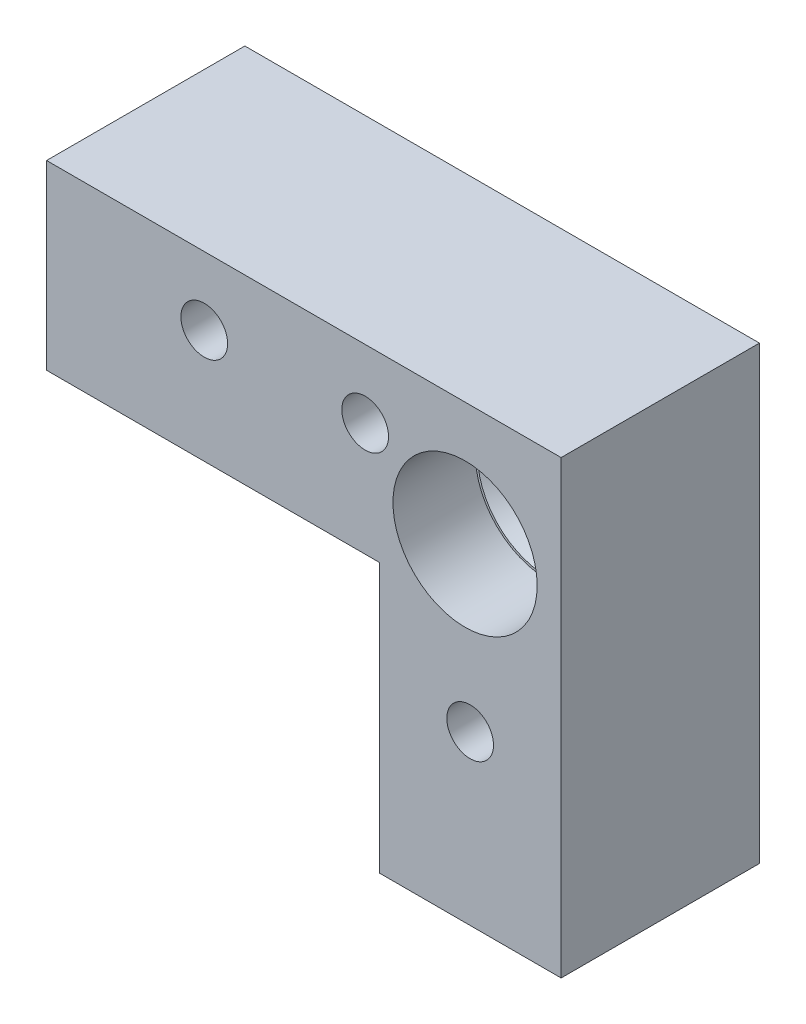
SolidWorks part; units mm, degrees
material "Rubber"
ref_plane "Front Plane" through (0, 0, 0) normal (0, 0, 1) x (1, 0, 0)
ref_plane "Top Plane" through (0, 0, 0) normal (0, 1, 0) x (1, 0, 0)
ref_plane "Right Plane" through (0, 0, 0) normal (1, 0, 0) x (0, 0, -1)
sketch "Sketch1" plane through (0, 0, 0) normal (0, 0, 1) x (1, 0, 0)
  line L1 (0, 0) -> (14, 0)
  line L2 (0, 0) -> (0, -34.73)
  line L3 (0, -34.73) -> (14, -34.73)
  line L4 (14, 0) -> (14, -34.73)
  line L5 (0, 0) -> (-25.65, 0)
  line L6 (0, 0) -> (0, -14)
  line L7 (0, -14) -> (-25.65, -14)
  line L8 (-25.65, 0) -> (-25.65, -14)
  dimension "D1" = 14
  dimension "D2" = 39.65
  dimension "D3" = 34.73
extrude "Boss-Extrude1" add sketch "Sketch1" along normal blind 42.65 contours L5 L8 L7 L2 | L4 L1 L2 L3 region at (7, -17.365, 0) region at (-12.825, -7, 0)
sketch "Sketch2" plane through (0, -14, 0) normal (0, -1, 0) x (1, 0, 0)
  line L0 (-25.65, 42.65) -> (-25.65, 0) construction
  line L1 (0, 42.65) -> (-25.65, 42.65) construction
  circle A0 centre (-14.665, 27.725) radius 6.425
  point P2 (-21.09, 27.725)
  point P6 (-14.665, 34.15)
  dimension "D1" = 12.85
  dimension "D2" = 4.56
  dimension "D3" = 8.5
extrude "Cut-Extrude1" cut sketch "Sketch2" against normal blind 42.65
sketch "Sketch3" plane through (0, -14, 0) normal (0, -1, 0) x (1, 0, 0)
  line L0 (0, 42.65) -> (-25.65, 42.65) construction
  line L1 (-17.65, 42.65) -> (-15.75, 42.65)
  line L2 (-17.65, 42.65) -> (-17.65, 12.65)
  line L3 (-17.65, 12.65) -> (-15.75, 12.65)
  line L4 (-15.75, 42.65) -> (-15.75, 12.65)
  line L5 (-25.65, 42.65) -> (-25.65, 0) construction
  dimension "D1" = 8
  dimension "D2" = 1.9
  dimension "D3" = 30
extrude "Cut-Extrude2" cut sketch "Sketch3" against normal blind 42.65
sketch "Sketch4" plane through (0, 0, 0) normal (-1, 0, 0) x (0, 0, 1)
  line L0 (42.65, -34.73) -> (0, -34.73) construction
  line L1 (42.65, -14) -> (42.65, -34.73) construction
  circle A0 centre (18.725, -21.745) radius 6.425
  point P2 (25.15, -21.745)
  point P3 (18.725, -28.17)
  dimension "D1" = 12.85
  dimension "D2" = 6.56
  dimension "D3" = 17.5
extrude "Cut-Extrude3" cut sketch "Sketch4" against normal blind 42.65
sketch "Sketch5" plane through (0, 0, 0) normal (-1, 0, 0) x (0, 0, 1)
  line L0 (42.65, -14) -> (42.65, -34.73) construction
  line L1 (42.65, -26.73) -> (10.65, -26.73)
  line L2 (42.65, -26.73) -> (42.65, -24.83)
  line L3 (42.65, -24.83) -> (10.65, -24.83)
  line L4 (10.65, -26.73) -> (10.65, -24.83)
  line L5 (42.65, -34.73) -> (0, -34.73) construction
  dimension "D1" = 8
  dimension "D2" = 1.9
  dimension "D3" = 32
extrude "Cut-Extrude4" cut sketch "Sketch5" against normal blind 42.65
hole_wizard "M3 Clearance Hole1" positions "Sketch6" profile "Sketch8" hole size "M3" standard "ANSI Metric"
sketch "Sketch6" plane through (0, 0, 0) normal (0, 0, -1) x (-1, 0, 0)
  line L0 (-14, 0) -> (25.65, 0) construction
  line L1 (25.65, 0) -> (25.65, -14) construction
  line L2 (-14, 0) -> (-14, -34.73) construction
  point P0 (1.1, -5.25)
  point P2 (13.5, -5.25)
  point P4 (-6.99, -21.8)
  dimension "D1" = 12.4
  dimension "D2" = 5.25
  dimension "D3" = 12.15
  dimension "D4" = 7.01
  dimension "D5" = 21.8
sketch "Sketch8" plane through (-1.1, -5.25, 0) normal (1, 0, 0) x (0, 1, 0)
  line L0 (0, 0) -> (0, 11.0815)
  line L1 (0, 11.0815) -> (1.8, 10)
  line L2 (1.8, 10) -> (1.8, 0.025)
  line L3 (1.8, 0.025) -> (1.825, 0)
  line L5 (1.825, 0) -> (0, 0)
  line L6 (-1.8, 0.025) -> (-1.825, 0) construction
  line L10 (0, 11.0815) -> (-1.8, 10) construction
  line L11 (0, -6.35) -> (0, 107.95) construction
  dimension "Hole Dia." = 3.6
  dimension "Hole Depth" = 10
  dimension "Near C'Sink Dia." = 3.65
  dimension "Near C'Sink Angle" = 90
  dimension "Drill Angle" = 118
ref_axis "Axis1" through (-14.665, 0.9766, 27.725) along (0, -1, 0)
ref_point "Point1"
ref_plane "Plane2" through (-14.665, 0, 0) normal (-1, 0, 0) x (0, 0, 1)
ref_point "Point2"
ref_plane "Plane3" through (0, 0, 18.725) normal (0, 0, -1) x (-1, 0, 0)
sketch "Sketch9" plane through (0, 0, 0) normal (0, 1, 0) x (1, 0, 0)
  line L0 (14, 0) -> (-25.65, 0) construction
  line L1 (-36.4186, -5.28) -> (25.575, -5.28)
  line L2 (-36.4186, -5.28) -> (-36.4186, -45.8335)
  line L3 (-36.4186, -45.8335) -> (25.575, -45.8335)
  line L4 (25.575, -5.28) -> (25.575, -45.8335)
  dimension "D1" = 5.28
extrude "Cut-Extrude5" cut sketch "Sketch9" against normal through all
sketch "Sketch10" plane through (0, 0, 0) normal (0, 0, -1) x (-1, 0, 0)
  line L6 (25.65, 0) -> (-14, 0)
  line L7 (-14, 0) -> (-14, -34.73)
  line L8 (-14, -34.73) -> (0, -34.73)
  line L9 (0, -34.73) -> (0, -14)
  line L10 (0, -14) -> (25.65, -14)
  line L11 (25.65, -14) -> (25.65, 0)
  line L12 (25.65, 0) -> (-14, 0)
  line L13 (-14, 0) -> (-14, -34.73)
  line L14 (-14, -34.73) -> (0, -34.73)
  line L15 (0, -34.73) -> (0, -14)
  line L16 (0, -14) -> (25.65, -14)
  line L17 (25.65, -14) -> (25.65, 0)
  circle A0 centre (1.1, -5.25) radius 1.825 construction
  circle A1 centre (1.1, -5.25) radius 1.825
  circle A2 centre (13.5, -5.25) radius 1.825 construction
  circle A3 centre (13.5, -5.25) radius 1.825
  circle A4 centre (-6.99, -21.8) radius 1.825 construction
  circle A5 centre (-6.99, -21.8) radius 1.825
  dimension "D1" = 0
extrude "Boss-Extrude2" add sketch "Sketch10" along normal blind 10
hole_wizard "CBORE for 1/4 Socket Head Cap Screw1" positions "Sketch11" profile "Sketch13" counterbore size "1/4" standard "ANSI Inch" end condition through all
sketch "Sketch11" plane through (0, 0, 5.28) normal (0, 0, 1) x (1, 0, 0)
  point P0 (6.5978, -9.4699)
  point P4 (6.5978, -9.4699)
sketch "Sketch13" plane through (6.5978, -9.4699, 5.28) normal (1, 0, 0) x (0, -1, 0)
  line L0 (0, 0) -> (0, 15.28)
  line L1 (0, 15.28) -> (3.3782, 15.28)
  line L3 (3.3782, 15.28) -> (3.3782, 6.35)
  line L4 (3.3782, 6.35) -> (5.5562, 6.35)
  line L5 (5.5562, 6.35) -> (5.5562, 0)
  line L7 (5.5562, 0) -> (0, 0)
  line L11 (0, -6.35) -> (0, 107.95) construction
  dimension "Thru Hole Dia." = 6.7564
  dimension "Thru Hole Depth" = 15.28
  dimension "C'Bore Dia." = 11.1125
  dimension "C'Bore Depth" = 6.35
sketch "Sketch14" plane through (0, 0, -10) normal (0, 0, -1) x (-1, 0, 0)
  circle A0 centre (1.1, -5.25) radius 5
  circle A1 centre (13.5, -5.25) radius 5
  circle A2 centre (-6.99, -21.8) radius 5
  dimension "D1" = 10
extrude "Cut-Extrude6" cut sketch "Sketch14" against normal blind 5
chamfer "Chamfer1" distance 2 angle 45 1 edges at (9.976, -9.4699, -1.07)
